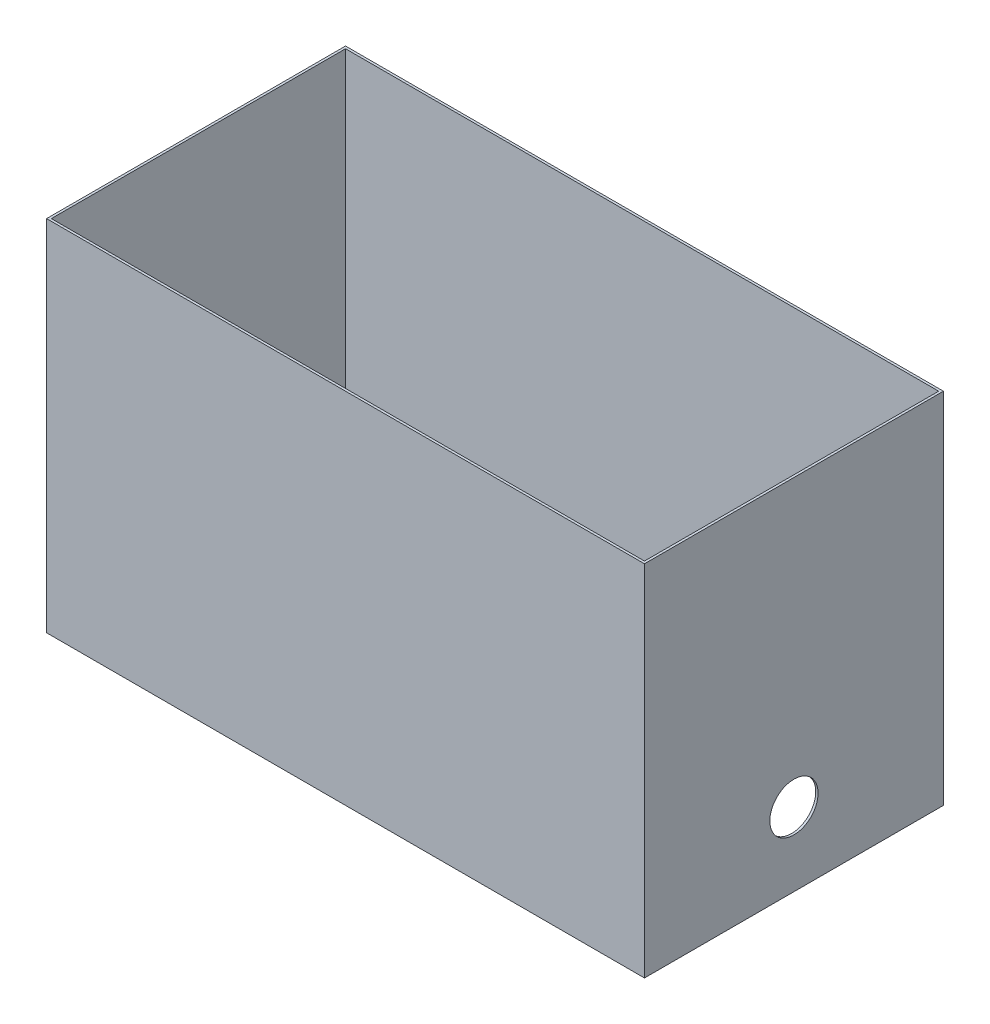
SolidWorks part; units mm, degrees
material "Galvanized Steel"
ref_plane "Front Plane" through (0, 0, 0) normal (0, 0, 1) x (1, 0, 0)
ref_plane "Top Plane" through (0, 0, 0) normal (0, 1, 0) x (1, 0, 0)
ref_plane "Right Plane" through (0, 0, 0) normal (1, 0, 0) x (0, 0, -1)
sketch "Sketch1" plane through (0, 0, 0) normal (0, 1, 0) x (1, 0, 0)
  line L0 (-252, 125) -> (252, 125)
  line L1 (-254, -127) -> (254, -127)
  line L2 (-254, -127) -> (-254, 127)
  line L3 (-254, 127) -> (254, 127)
  line L4 (254, -127) -> (254, 127)
  line L5 (-254, -127) -> (254, 127) construction
  line L6 (-254, 127) -> (254, -127) construction
  line L7 (252, -125) -> (252, 125)
  line L8 (-252, -125) -> (252, -125)
  line L9 (-252, -125) -> (-252, 125)
  point P0 (0, 0)
  dimension "D1" = 254
  dimension "D2" = 508
  dimension "D3" = 2
extrude "Boss-Extrude1" add sketch "Sketch1" along normal blind 304.8
sketch "Sketch2" plane through (-254, 0, 0) normal (-1, 0, 0) x (0, 0, 1)
  line L0 (0, 62.3) -> (0, 0) construction
  line L1 (-127, 0) -> (127, 0) construction
  circle A0 centre (0, 62.3) radius 20.5
  dimension "D1" = 62.3
  dimension "D2" = 41
extrude "Cut-Extrude1" cut sketch "Sketch2" against normal through all
